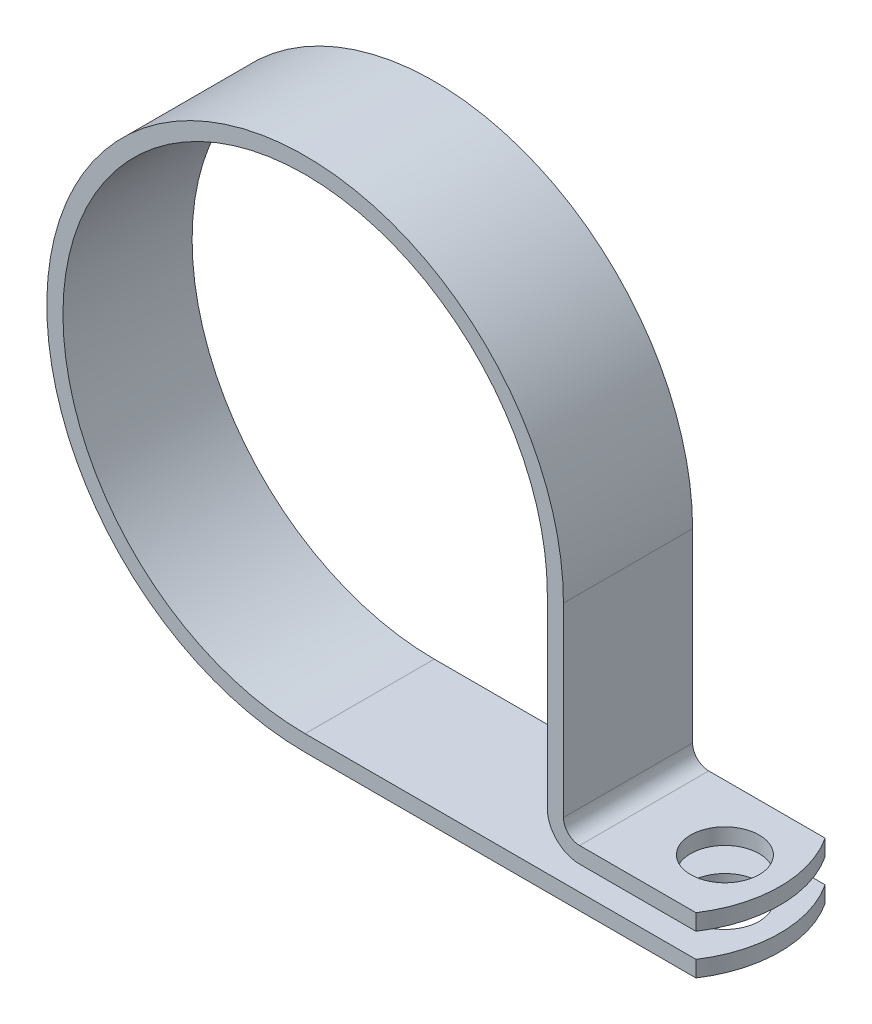
SolidWorks part; units mm, degrees
ref_plane "Front" through (0, 0, 0) normal (0, 0, 1) x (1, 0, 0)
ref_plane "Top" through (0, 0, 0) normal (0, 1, 0) x (1, 0, 0)
ref_plane "Right" through (0, 0, 0) normal (1, 0, 0) x (0, 0, -1)
sketch "Sketch1" plane through (0, 0, 0) normal (0, 0, 1) x (1, 0, 0)
  line L0 (0, -23.8125) -> (40.3352, -23.8125)
  line L1 (23.8125, 0) -> (23.8125, -18.2499)
  line L2 (26.9875, -21.4249) -> (40.3352, -21.4249)
  line L4 (26.9875, -19.8374) -> (40.3352, -19.8374)
  line L5 (25.4, 0) -> (25.4, -18.2499)
  line L6 (0, -25.4) -> (40.3352, -25.4)
  line L7 (40.3352, -19.8374) -> (40.3352, -21.4249)
  line L8 (40.3352, -23.8125) -> (40.3352, -25.4)
  arc A1 (26.9875, -21.4249) -> (23.8125, -18.2499) centre (26.9875, -18.2499) cw
  circle A2 centre (34.925, -21.4249) radius 3.3734 construction
  circle A3 centre (34.925, -21.4249) radius 4.7625 construction
  arc A4 (26.9875, -19.8374) -> (25.4, -18.2499) centre (26.9875, -18.2499) cw
  arc A5 (25.4, 0) -> (0, -25.4) centre (0, 0) ccw
  circle A6 centre (0, 0) radius 23.8125 construction
  arc A7 (23.8125, 0) -> (0, -23.8125) centre (0, 0) ccw
  arc A8 (23.8125, 0) -> (0, -23.8125) centre (0, 0) ccw construction
  dimension "D1" = 1.5875
extrude "Boss-Extrude1" add sketch "Sketch1" along normal mid plane 12.7
sketch "Sketch2" plane through (0, 0, 0) normal (0, 1, 0) x (1, 0, 0)
  circle A0 centre (34.925, 0) radius 3.3734
  dimension "D1" = 6.7469
extrude "Cut-Extrude1" cut sketch "Sketch2" against normal through all
sketch "Sketch4" plane through (0, 0, 0) normal (0, 1, 0) x (1, 0, 0)
  line L0 (40.3352, 6.35) -> (26.9875, 6.35) construction
  line L1 (40.3352, -6.35) -> (26.9875, -6.35) construction
  line L2 (40.3352, -6.35) -> (40.3352, 6.35) construction
  arc A0 (38.4302, 6.35) -> (38.4302, -6.35) centre (28.7994, 0) cw
  dimension "D1" = 1.905
extrude "Cut-Extrude3" cut sketch "Sketch4" against normal through all and the other way through all
sketch "Sketch3" [suppressed] plane through (0, -23.4442, 0) normal (0, -1, 0) x (1, 0, 0)
  line L0 (30.5594, 0) -> (32.9406, 0) construction
  line L1 (30.5594, 3.5719) -> (32.9406, 3.5719)
  line L2 (30.5594, -3.5719) -> (32.9406, -3.5719)
  arc A0 (30.5594, 3.5719) -> (30.5594, -3.5719) centre (30.5594, 0) ccw
  arc A1 (32.9406, -3.5719) -> (32.9406, 3.5719) centre (32.9406, 0) ccw
  circle A2 centre (31.75, 0) radius 3.5719 construction
  point P2 (31.75, 0)
  dimension "D1" = 9.525
extrude "Cut-Extrude2" [suppressed] cut sketch "Sketch3" against normal up to surface (1.2192 mm away)
sketch "Sketch7" [suppressed] plane through (0, 0, 0) normal (0, 0, 1) x (1, 0, 0)
  line L16 (46.501, -31.3817) -> (46.501, -25.781)
  line L17 (46.501, -25.781) -> (31.8072, -25.781)
  line L18 (31.3817, -25.3555) -> (31.3817, 0)
  line L19 (0, -31.3817) -> (46.501, -31.3817)
  line L21 (31.5209, -28.575) -> (0, -28.575)
  line L22 (28.575, 0) -> (28.575, -25.3555)
  line L26 (31.3817, -24.0915) -> (31.3817, 0)
  line L27 (0, -31.3817) -> (28.575, -31.3817)
  line L29 (28.575, -28.575) -> (0, -28.575)
  line L30 (28.575, 0) -> (28.575, -24.0915)
  arc A4 (28.575, -24.0915) -> (31.3817, -24.0915) centre (29.9783, -24.0915) ccw
  arc A5 (28.575, -28.575) -> (28.575, -31.3817) centre (28.575, -29.9784) cw
  arc A8 (31.3817, -25.3555) -> (31.8072, -25.781) centre (31.8072, -25.3555) ccw
  arc A9 (31.3817, 0) -> (0, -31.3817) centre (0, 0) ccw
  arc A10 (28.575, 0) -> (0, -28.575) centre (0, 0) ccw
  arc A11 (28.575, -25.3555) -> (31.5209, -28.575) centre (31.8072, -25.3555) ccw
  arc A13 (31.3817, 0) -> (0, -31.3817) centre (0, 0) ccw
  arc A14 (28.575, 0) -> (0, -28.575) centre (0, 0) ccw
  dimension "D1" = 0.7937
extrude "Boss-Extrude2" [suppressed] add sketch "Sketch7" along normal offset from surface 0.7937 and the other way offset from surface 0.7937 separate body offset beyond the face yes
fillet "Fillet1" [suppressed] radius 1.5875
move or copy body "Body-Move/Copy1" [suppressed] bodies to move or copy 111 copy yes number of copies 1 translate (0, 0, 0)
combine bodies "Combine1" [suppressed] operation type add bodies to combine 113 114
sketch "Ref1" plane through (0, 0, 0) normal (0, 1, 0) x (1, 0, 0)
  line L0 (0, 7.62) -> (0, -7.62)
  dimension "D1" = 15.24
sketch "Ref2" plane through (0, 0, 0) normal (0, 0, 1) x (1, 0, 0)
  line L0 (23.8125, 0) -> (23.8125, -23.8125)
  line L1 (23.8125, -23.8125) -> (0, -23.8125)
  circle A0 centre (0, 0) radius 23.8125 construction
  arc A1 (23.8125, 0) -> (0, -23.8125) centre (0, 0) ccw
  point P2 (23.8125, -18.2499)
equation "\"D1@Sketch1\" = \"Supplier G (thickness)@Sketch1\""
equation "\"D1@Sketch2\" = \"Hole Dia@Sketch1\""
equation "\"D1@Sketch3\" = \"Supplier S (slot)@Sketch1\""
equation "\"D1@Sketch4\" = \"Wd@Boss-Extrude1\" * .15"
equation "\"D1@Fillet1\" = ( \"Supplier G (thickness)@Sketch1\" + 0.0625) * .5"
equation "\"D1@Ref1\" = \"Wd@Boss-Extrude1\" * 1.2"
